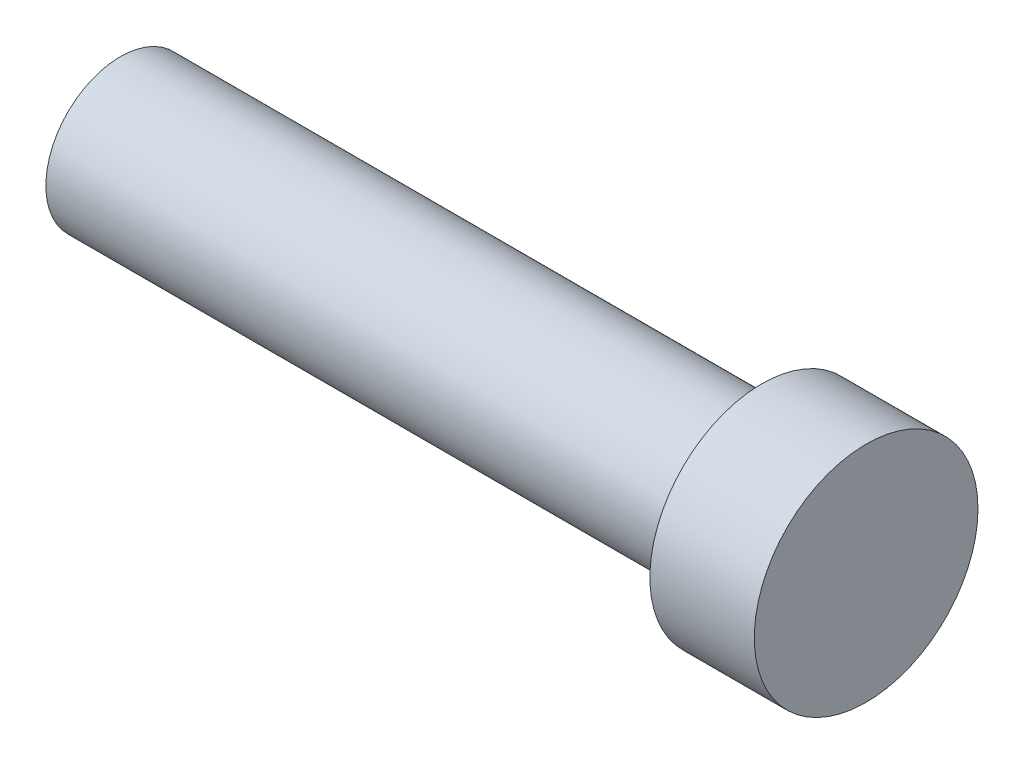
SolidWorks part; units mm, degrees
ref_plane "Front Plane" through (0, 0, 0) normal (0, 0, 1) x (1, 0, 0)
ref_plane "Top Plane" through (0, 0, 0) normal (0, 1, 0) x (1, 0, 0)
ref_plane "Right Plane" through (0, 0, 0) normal (1, 0, 0) x (0, 0, -1)
sketch "Sketch1" plane through (0, 0, 0) normal (1, 0, 0) x (0, 0, -1)
  circle A0 centre (0, 0) radius 7.5
  circle A1 centre (0, 0) radius 5
  dimension "D1" = 15
  dimension "D2" = 10
extrude "Boss-Extrude1" add sketch "Sketch1" against normal blind 7
extrude "Boss-Extrude2" add sketch "Sketch1<2>" against normal blind 50 contours A1 region at (0, 0, 0)
sketch "Sketch1<2>" plane through (0, 0, 0) normal (1, 0, 0) x (0, 0, -1) same geometry as "Sketch1"
